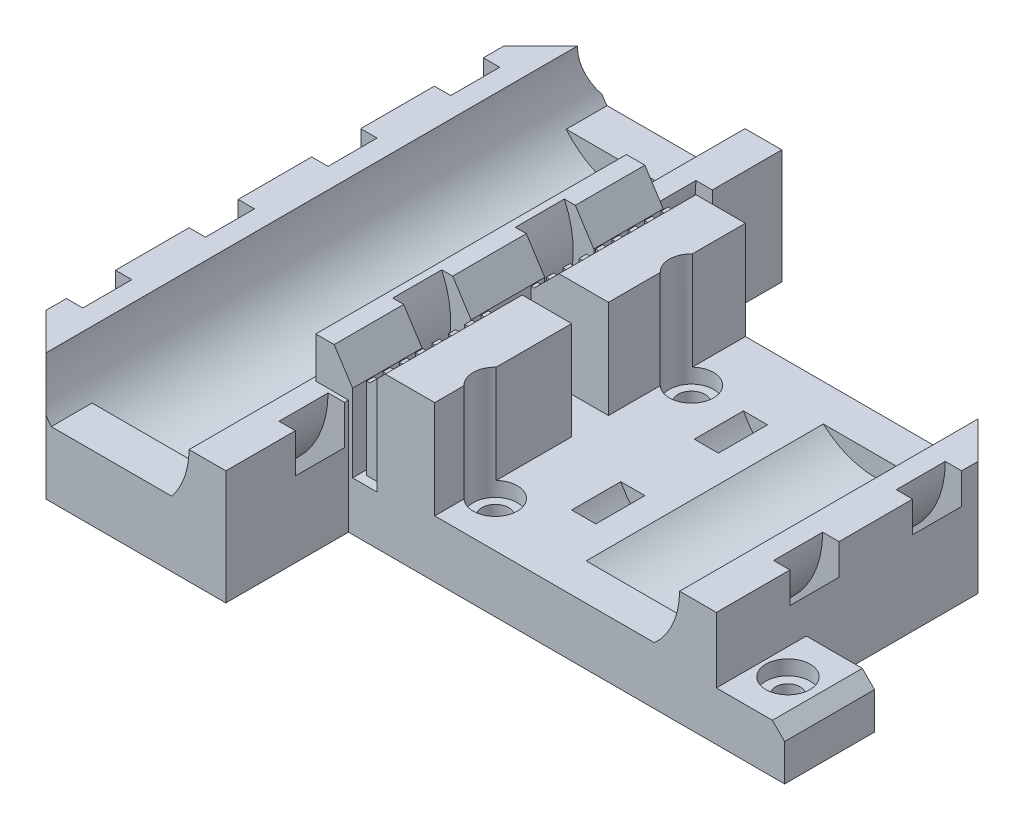
SolidWorks part; units mm, degrees
ref_plane "Front Plane" through (0, 0, 0) normal (0, 0, 1) x (1, 0, 0)
ref_plane "Top Plane" through (0, 0, 0) normal (0, 1, 0) x (1, 0, 0)
ref_plane "Right Plane" through (0, 0, 0) normal (1, 0, 0) x (0, 0, -1)
sketch "Sketch1" plane through (0, 0, 0) normal (0, 1, 0) x (1, 0, 0)
  line L0 (0.3879, -8.2154) -> (0.3879, 6.7846)
  line L1 (-27.6121, -8.2154) -> (0.3879, -8.2154)
  line L2 (-27.6121, -8.2154) -> (-27.6121, 59.7846)
  line L3 (-27.6121, 59.7846) -> (0.3879, 59.7846)
  line L4 (0.3879, 6.7846) -> (53.7379, 6.7846)
  line L5 (53.7379, 6.7846) -> (53.7379, 17.7846)
  line L6 (45.3879, 44.7846) -> (0.3879, 44.7846)
  line L7 (0.3879, 44.7846) -> (0.3879, 59.7846)
  line L8 (53.7379, 17.7846) -> (45.3879, 17.7846)
  line L9 (45.3879, 44.7846) -> (45.3879, 17.7846)
  circle A0 centre (12.7879, 36.3346) radius 1.65
  circle A1 centre (12.7879, 12.3346) radius 1.65
  circle A2 centre (48.5879, 12.3346) radius 1.5
  dimension "D10" = 3.3
  dimension "D13" = 3.3
  dimension "D15" = 3
  dimension "D1" = 68
  dimension "D2" = 28
  dimension "D3" = 15
  dimension "D4" = 15
  dimension "D5" = 53.35
  dimension "D6" = 28
  dimension "D7" = 45
  dimension "D8" = 11
  dimension "D9" = 24
  dimension "D11" = 40.4
  dimension "D12" = 40.4
  dimension "D14" = 8.45
  dimension "D16" = 32.45
  dimension "D17" = 35.8
extrude "Boss-Extrude1" add sketch "Sketch1" along normal blind 19
sketch "Sketch2" plane through (0, 19, 0) normal (0, 1, 0) x (1, 0, 0)
  line L1 (-27.6121, 59.7846) -> (0.3879, 59.7846)
  line L2 (-27.6121, 59.7846) -> (-27.6121, -8.2154)
  line L3 (-27.6121, -8.2154) -> (0.3879, -8.2154)
  line L4 (0.3879, 59.7846) -> (0.3879, -8.2154)
extrude "Cut-Extrude1" cut sketch "Sketch2" against normal blind 5
sketch "Sketch3" plane through (0, 0, 8.2154) normal (0, 0, 1) x (1, 0, 0)
  line L1 (-27.6121, 14) -> (0.3879, 14) construction
  line L2 (0.3879, 14) -> (0.3879, 0) construction
  circle A0 centre (-13.6121, 14) radius 9.5
  dimension "D2" = 19
  dimension "D1" = 0
  dimension "D3" = 14
extrude "Cut-Extrude2" cut sketch "Sketch3" against normal blind 79.7876
sketch "Sketch4" plane through (0, 0, 0) normal (0, -1, 0) x (1, 0, 0)
  line L0 (0.3879, 8.2154) -> (0.3879, -6.7846) construction
  line L1 (-27.6121, 8.2154) -> (0.3879, 8.2154)
  line L2 (-27.6121, 8.2154) -> (-27.6121, 3.2154)
  line L3 (-27.6121, 3.2154) -> (0.3879, 3.2154)
  line L4 (0.3879, 8.2154) -> (0.3879, 3.2154)
  line L5 (0.3879, -44.7846) -> (0.3879, -59.7846) construction
  line L6 (-27.6121, -59.7846) -> (0.3879, -59.7846)
  line L7 (-27.6121, -59.7846) -> (-27.6121, -54.7846)
  line L8 (-27.6121, -54.7846) -> (0.3879, -54.7846)
  line L9 (0.3879, -59.7846) -> (0.3879, -54.7846)
  dimension "D1" = 5
  dimension "D2" = 5
extrude "Boss-Extrude3" add sketch "Sketch4" against normal blind 8
sketch "Sketch5" plane through (0, 14, 0) normal (0, 1, 0) x (1, 0, 0)
  line L0 (-23.1121, 59.7846) -> (-23.1121, -8.2154) construction
  line L1 (-25.6121, 0.2846) -> (-28.4121, 0.2846)
  line L2 (-25.6121, 0.2846) -> (-25.6121, 6.2846)
  line L3 (-25.6121, 6.2846) -> (-28.4121, 6.2846)
  line L4 (-28.4121, 0.2846) -> (-28.4121, 6.2846)
  line L5 (-20.9776, -3.2154) -> (-6.2466, -3.2154) construction
  dimension "D1" = 6
  dimension "D2" = 2.8
  dimension "D3" = 2.5
  dimension "D4" = 3.5
ref_axis "Axis1" through (-13.6121, 14, -59.7846) along (0, 0, 1)
revolve "Cut-Revolve2" cut sketch "Sketch5" angle 360 about axis through (-13.6121, 14, -59.7846) along (0, 0, 1)
sketch "Sketch7" plane through (0, 14, 0) normal (0, 1, 0) x (1, 0, 0)
  line L0 (0.3879, 44.7846) -> (0.3879, 6.7846)
  line L1 (0.3879, 44.7846) -> (-3.6121, 44.7846)
  line L2 (0.3879, 6.7846) -> (-3.6121, 6.7846)
  line L3 (-3.6121, 44.7846) -> (-3.6121, 6.7846)
  dimension "D1" = 4
extrude "Boss-Extrude4" add sketch "Sketch7" along normal blind 5
sketch "Sketch8" plane through (0, 19, 0) normal (0, 1, 0) x (1, 0, 0)
  line L0 (-3.6121, 6.7846) -> (53.7379, 6.7846) construction
  line L1 (0.8879, 6.7846) -> (1.4879, 6.7846)
  line L2 (0.8879, 6.7846) -> (0.8879, 44.7846)
  line L3 (0.8879, 44.7846) -> (1.4879, 44.7846)
  line L4 (1.4879, 6.7846) -> (1.4879, 44.7846)
  line L5 (45.3879, 44.7846) -> (-3.6121, 44.7846) construction
  line L6 (0.3879, 44.7846) -> (0.3879, 59.7846) construction
  dimension "D1" = 0.5
  dimension "D2" = 0.6
extrude "Cut-Extrude3" cut sketch "Sketch8" against normal blind 13
pattern_linear "LPattern1" count 4 spacing 15 along (0, 0, -1) of "Cut-Revolve2"
sketch "Sketch9" plane through (0, 0, -6.7846) normal (0, 0, 1) x (1, 0, 0)
  line L0 (0.8879, 19) -> (-1.3621, 19)
  line L1 (0.8879, 6) -> (0.8879, 19) construction
  line L2 (-3.6121, 19) -> (0.8879, 19) construction
  line L3 (-1.3621, 19) -> (0.8879, 15.5)
  line L4 (0.8879, 15.5) -> (0.8879, 19)
extrude "Cut-Extrude4" cut sketch "Sketch9" against normal blind 54
sketch "Sketch11" plane through (0, 0, -6.7846) normal (0, 0, 1) x (1, 0, 0)
  line L0 (0.3879, 0) -> (53.7379, 0) construction
  circle A0 centre (31.3879, 14) radius 9.5
  dimension "D1" = 19
  dimension "D2" = 45
  dimension "D3" = 14
extrude "Cut-Extrude6" cut sketch "Sketch11" along direction (0, 0, -1) on the side against the normal offset from surface (75 mm away) 75 up to face at (9.4924, 11.9545, -6.7846)
ref_axis "Axis2" through (31.3879, 14, -44.7846) along (0, 0, 1)
sketch "Sketch12" plane through (0, 19, 0) normal (0, 1, 0) x (1, 0, 0)
  line L0 (23.3101, 44.7846) -> (1.4879, 44.7846) construction
  line L1 (10.9379, 44.7846) -> (31.3879, 44.7846)
  line L2 (10.9379, 44.7846) -> (10.9379, 6.7846)
  line L3 (10.9379, 6.7846) -> (31.3879, 6.7846)
  line L4 (31.3879, 44.7846) -> (31.3879, 6.7846)
  line L5 (31.3879, 44.7846) -> (31.3879, 6.7846) construction
  line L6 (1.4879, 6.7846) -> (1.4879, 44.7846) construction
  dimension "D1" = 0
  dimension "D2" = 9.45
extrude "Cut-Extrude7" cut sketch "Sketch12" against normal blind 12
sketch "Sketch14" plane through (0, 19, 0) normal (0, 1, 0) x (1, 0, 0)
  line L1 (39.4656, 44.7846) -> (53.7379, 44.7846)
  line L2 (39.4656, 44.7846) -> (39.4656, 6.7846)
  line L3 (39.4656, 6.7846) -> (53.7379, 6.7846)
  line L4 (53.7379, 44.7846) -> (53.7379, 6.7846)
extrude "Cut-Extrude9" cut sketch "Sketch14" against normal blind 5
sketch "Sketch15" plane through (0, 14, 0) normal (0, 1, 0) x (1, 0, 0)
  line L0 (40.8879, 6.7846) -> (53.7379, 6.7846) construction
  line L1 (53.7379, 17.7846) -> (45.3879, 17.7846)
  line L2 (53.7379, 17.7846) -> (53.7379, 6.7846)
  line L3 (53.7379, 6.7846) -> (45.3879, 6.7846)
  line L4 (45.3879, 17.7846) -> (45.3879, 6.7846)
extrude "Cut-Extrude10" cut sketch "Sketch15" against normal blind 8
sketch "Sketch16" plane through (0, 0, 0) normal (0, -1, 0) x (-1, 0, 0)
  line L0 (-0.3879, 6.7846) -> (-53.7379, 6.7846) construction
  line L1 (-44.6036, 6.7846) -> (-16.2094, 6.7846)
  line L2 (-44.6036, 6.7846) -> (-44.6036, 11.2846)
  line L3 (-44.6036, 11.2846) -> (-16.2094, 11.2846)
  line L4 (-16.2094, 6.7846) -> (-16.2094, 11.2846)
  line L6 (-45.3879, 44.7846) -> (-21.7206, 44.7846)
  line L7 (-45.3879, 44.7846) -> (-45.3879, 40.2846)
  line L8 (-45.3879, 40.2846) -> (-21.7206, 40.2846)
  line L9 (-21.7206, 44.7846) -> (-21.7206, 40.2846)
  dimension "D1" = 4.5
  dimension "D2" = 4.5
extrude "Boss-Extrude5" add sketch "Sketch16" against normal blind 7
sketch "Sketch17" plane through (0, 14, 0) normal (0, 1, 0) x (1, 0, 0)
  line L0 (40.8879, 44.7846) -> (40.8879, 6.7846) construction
  line L1 (43.3879, 21.7846) -> (45.8879, 21.7846)
  line L2 (43.3879, 21.7846) -> (43.3879, 15.7846)
  line L3 (43.3879, 15.7846) -> (45.8879, 15.7846)
  line L4 (45.8879, 21.7846) -> (45.8879, 15.7846)
  line L5 (24.9653, 11.2846) -> (37.8105, 11.2846) construction
  dimension "D1" = 2.5
  dimension "D2" = 6
  dimension "D3" = 2.5
  dimension "D4" = 4.5
revolve "Cut-Revolve3" cut sketch "Sketch17" angle 360 about axis through (31.3879, 14, -44.7846) along (0, 0, 1)
pattern_linear "LPattern2" count 2 spacing 15 along (0, 0, -1) of "Cut-Revolve3"
sketch "Sketch18" plane through (0, 6, 0) normal (0, 1, 0) x (1, 0, 0)
  circle A0 centre (48.5879, 12.3346) radius 2.7
  dimension "D1" = 5.4
extrude "Cut-Extrude11" cut sketch "Sketch18" against normal blind 1.8
sketch "Sketch19" plane through (0, 7, 0) normal (0, 1, 0) x (1, 0, 0)
  circle A0 centre (12.7879, 36.3346) radius 2.7
  circle A1 centre (12.7879, 12.3346) radius 2.7
  dimension "D1" = 5.4
  dimension "D2" = 5.4
extrude "Cut-Extrude12" cut sketch "Sketch19" against normal blind 13.8 from offset 12
sketch "Sketch20" plane through (0, 19, 0) normal (0, 1, 0) x (1, 0, 0)
  line L0 (1.4879, 6.7846) -> (1.4879, 44.7846) construction
  line L1 (3.8879, 42.7846) -> (1.4879, 42.7846)
  line L2 (3.8879, 42.7846) -> (3.8879, 43.8946)
  line L3 (3.8879, 43.8946) -> (1.4879, 43.8946)
  line L4 (1.4879, 42.7846) -> (1.4879, 43.8946)
  line L5 (10.9379, 44.7846) -> (1.4879, 44.7846) construction
  dimension "D1" = 1.11
  dimension "D2" = 2.4
  dimension "D3" = 0.89
extrude "Cut-Extrude13" cut sketch "Sketch20" against normal up to surface (13 mm away) up to face at (1.1879, 6, -25.7846)
pattern_linear "LPattern3" count 20 spacing 2 along (0, 0, 1) of "Cut-Extrude13"
sketch "Sketch23" plane through (0, 0, -6.7846) normal (0, 0, 1) x (1, 0, 0)
  line L1 (10.9379, 19) -> (1.2977, 19)
  line L2 (10.9379, 19) -> (10.9379, 7)
  line L3 (10.9379, 7) -> (1.2977, 7)
  line L4 (1.2977, 19) -> (1.2977, 7)
extrude "Cut-Extrude15" cut sketch "Sketch23" against normal mid plane 4.5 from offset 19 offset against normal yes
chamfer "Chamfer2" distance 1.5 angle 45 1 edges at (53.7379, 6, -12.2846)
chamfer "Chamfer3" distance 6 angle 45 3 edges at (45.3879, 7, -44.7846) (-27.6121, 7, -59.7846) (-27.6121, 7, 8.2154)
sketch "Sketch24" plane through (0, 0, -44.7846) normal (0, 0, -1) x (-1, 0, 0)
  line L0 (-1.4879, 19) -> (-1.4879, 16)
  line L1 (-1.4879, 6) -> (-1.4879, 19) construction
  line L2 (-1.4879, 16) -> (-1.8879, 16)
  line L3 (-1.8879, 16) -> (-4.8879, 19)
  line L4 (-10.9379, 19) -> (-1.4879, 19) construction
  line L5 (-4.8879, 19) -> (-1.4879, 19)
  dimension "D1" = 3
  dimension "D2" = 0.4
extrude "Cut-Extrude16" cut sketch "Sketch24" against normal blind 56
